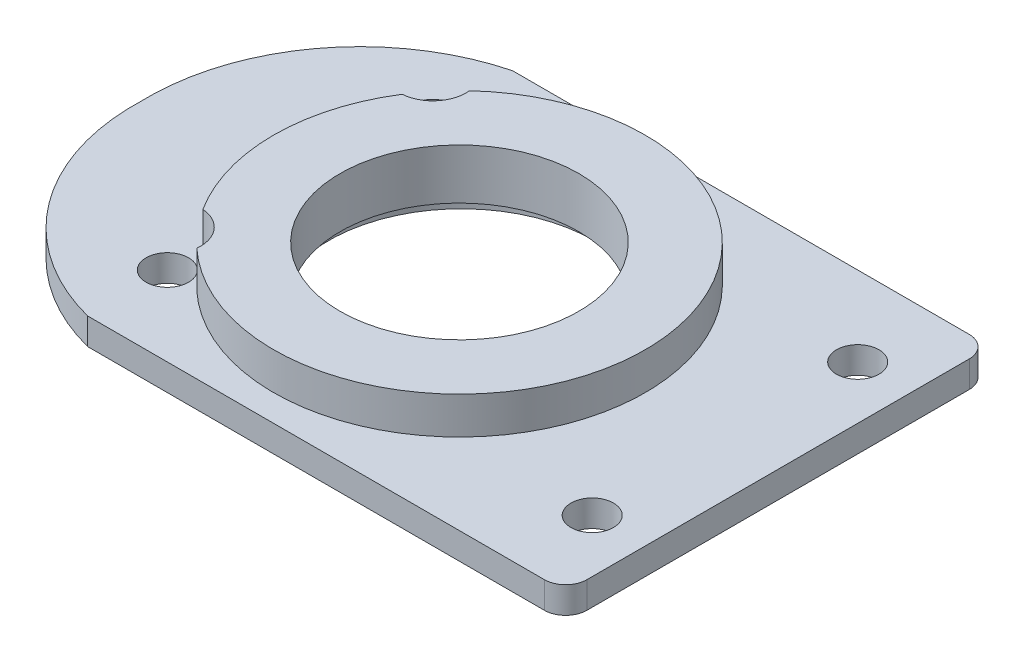
SolidWorks part; units mm, degrees
ref_plane "Front Plane" through (0, 0, 0) normal (0, 0, 1) x (1, 0, 0)
ref_plane "Top Plane" through (0, 0, 0) normal (0, 1, 0) x (1, 0, 0)
ref_plane "Right Plane" through (0, 0, 0) normal (1, 0, 0) x (0, 0, -1)
sketch "Sketch1" plane through (0, 0, 0) normal (0, 1, 0) x (1, 0, 0)
  line L1 (0, 0) -> (76.2, 0)
  line L2 (0, 0) -> (0, 50.8)
  line L3 (0, 50.8) -> (76.2, 50.8)
  line L4 (76.2, 0) -> (76.2, 50.8)
  circle A0 centre (38.1, 25.4) radius 14.2748
  dimension "D5" = 28.5496
  dimension "D1" = 50.8
  dimension "D2" = 76.2
  dimension "D3" = 38.1
  dimension "D4" = 25.4
extrude "Boss-Extrude1" add sketch "Sketch1" along normal blind 3.175
sketch "Sketch2" plane through (0, 3.175, 0) normal (0, 1, 0) x (1, 0, 0)
  circle A0 centre (38.1, 25.4) radius 22.225
  dimension "D1" = 44.45
extrude "Boss-Extrude2" add sketch "Sketch2" along normal blind 4.445
sketch "Sketch3" plane through (0, 3.175, 0) normal (0, -1, 0) x (1, 0, 0)
  circle A1 centre (38.1, -25.4) radius 14.2748
  circle A2 centre (38.1, -25.4) radius 14.2748
  dimension "D1" = 0
extrude "Cut-Extrude1" cut sketch "Sketch3" against normal through all
sketch "Sketch4" plane through (0, 0, 0) normal (0, -1, 0) x (-1, 0, 0)
  line L0 (0, 0) -> (-76.2, 0) construction
  circle A0 centre (-38.3325, 25.4) radius 15.8623
  dimension "D1" = 31.7246
  dimension "D2" = 25.4
extrude "Cut-Extrude2" cut sketch "Sketch4" against normal blind 1.6002
fillet "Fillet2" radius 2.54 4 edges at (0, 1.5875, -50.8) (76.2, 1.5875, -50.8) (0, 1.5875, 0) (76.2, 1.5875, 0)
sketch "Sketch5" plane through (0, 3.175, 0) normal (0, 1, 0) x (1, 0, 0)
  line L0 (73.66, 50.8) -> (2.54, 50.8) construction
  line L2 (2.54, 0) -> (73.66, 0) construction
  line L3 (76.2, 2.54) -> (76.2, 48.26) construction
  circle A0 centre (69.85, 41.275) radius 2.54
  circle A1 centre (69.85, 9.525) radius 2.54
  circle A2 centre (19.05, 9.525) radius 2.54
  circle A3 centre (19.05, 41.275) radius 2.54
  dimension "D9" = 5.08
  dimension "D10" = 5.08
  dimension "D11" = 5.08
  dimension "D12" = 5.08
  dimension "D1" = 9.525
  dimension "D2" = 50.8
  dimension "D3" = 50.8
  dimension "D4" = 9.525
  dimension "D5" = 9.525
  dimension "D6" = 6.35
  dimension "D7" = 9.525
  dimension "D8" = 6.35
extrude "Cut-Extrude3" cut sketch "Sketch5" against normal through all and the other way through all
sketch "Sketch6" plane through (0, 3.175, 0) normal (0, 1, 0) x (1, 0, 0)
  line L0 (2.54, 0) -> (73.66, 0) construction
  line L1 (0, 48.26) -> (0, 2.54) construction
  line L2 (73.66, 50.8) -> (2.54, 50.8) construction
  line L3 (19.05, 0) -> (0, 0)
  line L4 (0, 0) -> (0, 25.4)
  line L5 (19.05, 50.8) -> (0, 50.8)
  line L6 (0, 50.8) -> (0, 25.4)
  arc A0 (19.05, 0) -> (0, 25.4) centre (25.3873, 24.5967) cw
  arc A1 (19.05, 50.8) -> (0, 25.4) centre (25.3873, 26.2033) ccw
  line M6 (73.66, 50.8) -> (2.54, 50.8)
  arc M7 (2.54, 50.8) -> (0, 48.26) centre (2.54, 48.26) ccw
  line M8 (0, 48.26) -> (0, 2.54)
  arc M9 (0, 2.54) -> (2.54, 0) centre (2.54, 2.54) ccw
  line M10 (2.54, 0) -> (73.66, 0)
extrude "Cut-Extrude4" cut sketch "Sketch6" against normal through all contours A1 M6 M7 M8 | A0 L4 M10 M9 region at (5.0302, 3.175, -45.1477) region at (5.0302, 3.175, -5.6523)
sketch "Sketch7" plane through (0, 3.175, 0) normal (0, 1, 0) x (1, 0, 0)
  circle A0 centre (19.05, 9.525) radius 3.9688
  dimension "D1" = 7.9375
extrude "Cut-Extrude5" cut sketch "Sketch7" along normal through all contours A0
sketch "Sketch9" plane through (0, 3.175, 0) normal (0, 1, 0) x (1, 0, 0)
  circle A0 centre (19.05, 41.275) radius 3.9688
  dimension "D1" = 7.9375
extrude "Cut-Extrude6" cut sketch "Sketch9" along normal through all contours A0
